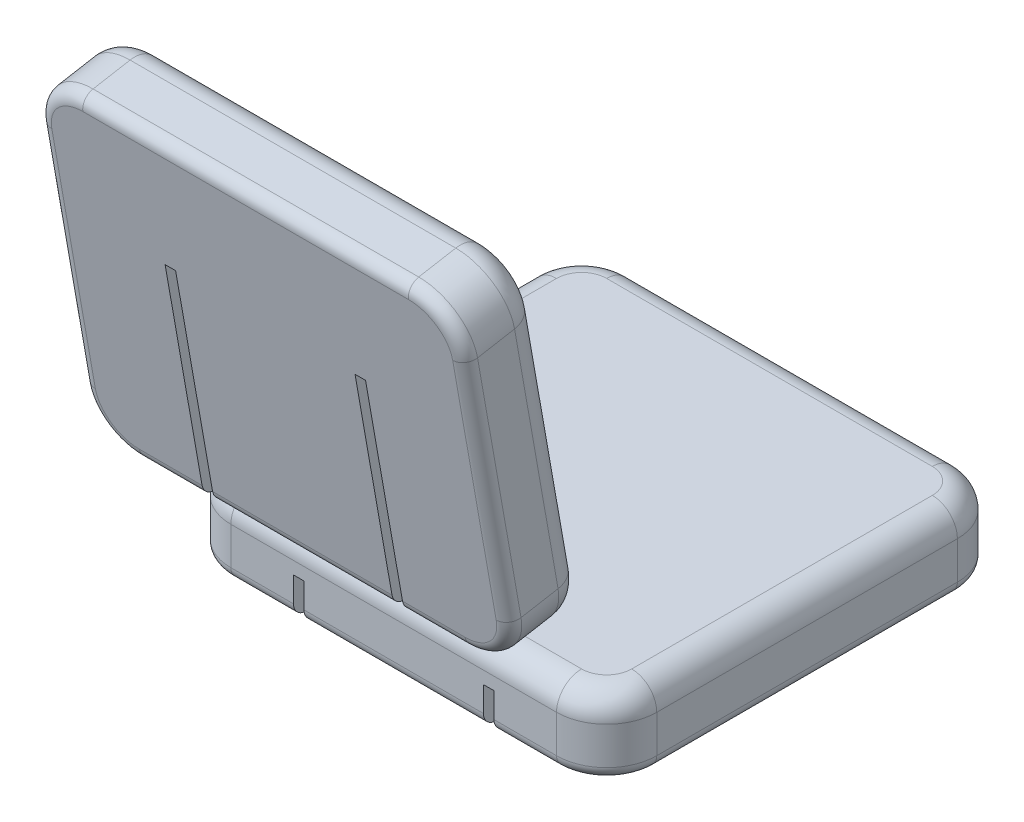
SolidWorks part; units mm, degrees
other "cushion_back"
other "cushion_bottom"
ref_plane "Front" through (0, 0, 0) normal (0, 0, 1) x (1, 0, 0)
ref_plane "Top" through (0, 0, 0) normal (0, 1, 0) x (1, 0, 0)
ref_plane "Right" through (0, 0, 0) normal (1, 0, 0) x (0, 0, -1)
sketch "Sketch1" plane through (0, 0, 0) normal (1, 0, 0) x (0, 0, -1)
  line L0 (-84.1955, -182.4) -> (-80, -182.4) construction
  line L1 (-136.5723, -4.3259) -> (-108.8157, -161.7412) construction
  line L2 (-131.2503, -34.5085) -> (-136.5723, -4.3259) construction
  line L3 (-116.4781, -31.9038) -> (-131.2503, -34.5085) construction
  line L4 (-94.0436, -159.1365) -> (-116.4781, -31.9038) construction
  line L5 (-84.1955, -167.4) -> (-80, -167.4) construction
  line L6 (185.7877, -52.3656) -> (265.7877, -52.3656) construction
  line L7 (265.7877, -52.3656) -> (258.3511, -137.3656) construction
  line L8 (258.3511, -137.3656) -> (193.2242, -137.3656) construction
  line L9 (40, -182.4) -> (40, -252.4) construction
  line L10 (-70, -182.4) -> (-70, -212.4) construction
  line L11 (-86.0777, -117.9317) -> (-110.3884, 19.9414) construction
  line L12 (-110.3884, 19.9414) -> (-139.9327, 14.7319) construction
  line L13 (-139.9327, 14.7319) -> (-115.6219, -123.1412) construction
  line L14 (-86.0777, -117.9317) -> (-115.6219, -123.1412) construction
  line L15 (-80, -152.4) -> (-80, -182.4) construction
  line L16 (80, -152.4) -> (-80, -152.4) construction
  line L17 (80, -152.4) -> (80, -182.4) construction
  line L18 (80, -182.4) -> (-80, -182.4) construction
  line L19 (165.8638, -54.1087) -> (185.7877, -52.3656) construction
  line L20 (165.8638, -54.1087) -> (183.2949, -253.3477) construction
  line L21 (183.2949, -253.3477) -> (203.2188, -251.6045) construction
  line L22 (203.2188, -251.6045) -> (185.7877, -52.3656) construction
  line L23 (-105, -212.4) -> (-135, -242.4) construction
  line L24 (-135, -242.4) -> (-137, -242.4) construction
  line L25 (-137, -242.4) -> (-137, -272.4) construction
  line L26 (-137, -272.4) -> (252, -272.4) construction
  line L27 (252, -272.4) -> (252, -242.4) construction
  line L28 (252, -242.4) -> (250, -242.4) construction
  line L29 (250, -242.4) -> (220, -212.4) construction
  line L30 (220, -212.4) -> (170, -212.4) construction
  line L31 (170, -212.4) -> (130, -252.4) construction
  line L32 (130, -252.4) -> (-15, -252.4) construction
  line L33 (-15, -252.4) -> (-55, -212.4) construction
  line L34 (-55, -212.4) -> (-105, -212.4) construction
  line L35 (-84.1955, -182.4) -> (-80, -182.4)
  line L36 (-136.5723, -4.3259) -> (-108.8157, -161.7412)
  line L37 (-131.2503, -34.5085) -> (-136.5723, -4.3259)
  line L38 (-116.4781, -31.9038) -> (-131.2503, -34.5085)
  line L39 (-94.0436, -159.1365) -> (-116.4781, -31.9038)
  line L40 (-84.1955, -167.4) -> (-80, -167.4)
  line L41 (185.7877, -52.3656) -> (265.7877, -52.3656)
  line L42 (265.7877, -52.3656) -> (258.3511, -137.3656)
  line L43 (258.3511, -137.3656) -> (193.2242, -137.3656)
  line L44 (40, -182.4) -> (40, -252.4)
  line L45 (-70, -182.4) -> (-70, -212.4)
  line L46 (-86.0777, -117.9317) -> (-110.3884, 19.9414)
  line L47 (-110.3884, 19.9414) -> (-139.9327, 14.7319)
  line L48 (-139.9327, 14.7319) -> (-115.6219, -123.1412)
  line L49 (-86.0777, -117.9317) -> (-115.6219, -123.1412)
  line L50 (-80, -152.4) -> (-80, -182.4)
  line L51 (80, -152.4) -> (-80, -152.4)
  line L52 (80, -152.4) -> (80, -182.4)
  line L53 (80, -182.4) -> (-80, -182.4)
  line L54 (165.8638, -54.1087) -> (185.7877, -52.3656)
  line L55 (165.8638, -54.1087) -> (183.2949, -253.3477)
  line L56 (183.2949, -253.3477) -> (203.2188, -251.6045)
  line L57 (203.2188, -251.6045) -> (185.7877, -52.3656)
  line L58 (-105, -212.4) -> (-135, -242.4)
  line L59 (-135, -242.4) -> (-137, -242.4)
  line L60 (-137, -242.4) -> (-137, -272.4)
  line L61 (-137, -272.4) -> (252, -272.4)
  line L62 (252, -272.4) -> (252, -242.4)
  line L63 (252, -242.4) -> (250, -242.4)
  line L64 (250, -242.4) -> (220, -212.4)
  line L65 (220, -212.4) -> (170, -212.4)
  line L66 (170, -212.4) -> (130, -252.4)
  line L67 (130, -252.4) -> (-15, -252.4)
  line L68 (-15, -252.4) -> (-55, -212.4)
  line L69 (-55, -212.4) -> (-105, -212.4)
  arc A0 (-108.8157, -161.7412) -> (-84.1955, -182.4) centre (-84.1955, -157.4) ccw construction
  arc A1 (-94.0436, -159.1365) -> (-84.1955, -167.4) centre (-84.1955, -157.4) ccw construction
  circle A2 centre (195, -272.4) radius 37.5 construction
  circle A3 centre (-80, -272.4) radius 37.5 construction
  arc A4 (-108.8157, -161.7412) -> (-84.1955, -182.4) centre (-84.1955, -157.4) ccw
  arc A5 (-94.0436, -159.1365) -> (-84.1955, -167.4) centre (-84.1955, -157.4) ccw
  circle A6 centre (195, -272.4) radius 37.5
  circle A7 centre (-80, -272.4) radius 37.5
extrude "Boss-Extrude1" add sketch "Sketch1" along normal mid plane 170 contours L53 L52 L51 L50 | L49 L46 L47 L48 L36 L38 L39 | L49 L39 L38 L36 region at (0, -167.4, 0) region at (0, -77.5225, 116.05) region at (0, -39.3208, 111.5629)
fillet "Fillet5" radius 5 4 edges at (0, 14.7319, 139.9327) (85, -54.2046, 127.7773) (0, -123.1412, 115.6219) (-85, -54.2046, 127.7773)
fillet "Fillet6" radius 5 4 edges at (0, -182.4, 80) (85, -182.4, 0) (0, -182.4, -80) (-85, -182.4, 0)
sketch "Sketch2" plane through (0, 0, 0) normal (1, 0, 0) x (0, 0, -1)
  line L0 (-136.5723, -4.3259) -> (-108.8157, -161.7412) construction
  line L1 (-84.1955, -167.4) -> (-80, -167.4) construction
  line L2 (-94.0436, -159.1365) -> (-116.4781, -31.9038) construction
  line L3 (-116.4781, -31.9038) -> (-131.2503, -34.5085) construction
  line L5 (-84.1955, -182.4) -> (-80, -182.4) construction
  line L6 (-131.2503, -34.5085) -> (-108.8157, -161.7412)
  line L7 (-84.1955, -167.4) -> (-80, -167.4)
  line L8 (-94.0436, -159.1365) -> (-116.4781, -31.9038)
  line L9 (-116.4781, -31.9038) -> (-131.2503, -34.5085)
  line L10 (-80, -167.4) -> (20, -167.4)
  line L11 (-84.1955, -182.4) -> (-80, -182.4)
  line L12 (20, -167.4) -> (20, -182.4)
  line L13 (20, -182.4) -> (-80, -182.4)
  line L14 (80, -152.4) -> (80, -182.4) construction
  arc A0 (-94.0436, -159.1365) -> (-84.1955, -167.4) centre (-84.1955, -157.4) ccw construction
  arc A1 (-108.8157, -161.7412) -> (-84.1955, -182.4) centre (-84.1955, -157.4) ccw construction
  arc A2 (-94.0436, -159.1365) -> (-84.1955, -167.4) centre (-84.1955, -157.4) ccw
  arc A3 (-108.8157, -161.7412) -> (-84.1955, -182.4) centre (-84.1955, -157.4) ccw
  dimension "D1" = 60
extrude "Cut-Extrude1" cut sketch "Sketch2" along normal blind 4.2 from offset 40 offset against normal yes
mirror "Mirror1" about plane through (0, 0, 0) normal (1, 0, 0) of "Cut-Extrude1"
fillet "Fillet1" radius 20 8 edges at (85, -164.9, -80) (85, -164.9, 80) (-85, -164.9, 80) (-85, -164.9, -80) (-83.5355, -180.9355, -78.5355) (-83.5355, -180.9355, 78.5355) (83.5355, -180.9355, 78.5355) (83.5355, -180.9355, -78.5355)
fillet "Fillet2" radius 20 8 edges at (85, -120.1023, 98.3878) (85, 17.7708, 122.6985) (-85, -120.1023, 98.3878) (-85, 17.7708, 122.6985) (-83.5355, 13.544, 138.2361) (-83.5355, -121.4447, 114.434) (83.5355, 13.544, 138.2361) (83.5355, -121.4447, 114.434)
fillet "Fillet3" radius 10 8 edges at (79.1421, 14.1725, 109.3712) (0, 19.9414, 110.3884) (-79.1421, 14.1725, 109.3712) (-85, -48.9952, 98.2331) (-79.1421, -112.1629, 87.0949) (0, -117.9317, 86.0777) (79.1421, -112.1629, 87.0949) (85, -48.9952, 98.2331)
fillet "Fillet4" radius 10 8 edges at (79.1421, -152.4, 74.1421) (0, -152.4, 80) (-79.1421, -152.4, 74.1421) (-85, -152.4, 0) (-79.1421, -152.4, -74.1421) (0, -152.4, -80) (79.1421, -152.4, -74.1421) (85, -152.4, 0)
sketch "Sketch3" plane through (0, -182.4, 0) normal (0, -1, 0) x (1, 0, 0)
  line L0 (-25.2, 30) -> (-25.2, 0)
  line L1 (-20, -5.2) -> (20, -5.2)
  line L2 (25.2, 0) -> (25.2, 30)
  line L3 (20, 35.2) -> (-20, 35.2)
  line L4 (20, 35) -> (-20, 35)
  line L5 (-25, 30) -> (-25, 0)
  line L6 (-20, -5) -> (20, -5)
  line L7 (25, 0) -> (25, 30)
  line L8 (20, 35) -> (-20, 35) construction
  line L9 (-25, 30) -> (-25, 0) construction
  line L10 (-20, -5) -> (20, -5) construction
  line L11 (25, 0) -> (25, 30) construction
  arc A0 (-25.2, 0) -> (-20, -5.2) centre (-20, 0) ccw
  arc A1 (20, -5.2) -> (25.2, 0) centre (20, 0) ccw
  arc A2 (25.2, 30) -> (20, 35.2) centre (20, 30) ccw
  arc A3 (-20, 35.2) -> (-25.2, 30) centre (-20, 30) ccw
  arc A4 (-20, 35) -> (-25, 30) centre (-20, 30) ccw
  arc A5 (-25, 0) -> (-20, -5) centre (-20, 0) ccw
  arc A6 (20, -5) -> (25, 0) centre (20, 0) ccw
  arc A7 (25, 30) -> (20, 35) centre (20, 30) ccw
  arc A8 (-20, 35) -> (-25, 30) centre (-20, 30) ccw construction
  arc A9 (-25, 0) -> (-20, -5) centre (-20, 0) ccw construction
  arc A10 (20, -5) -> (25, 0) centre (20, 0) ccw construction
  arc A11 (25, 30) -> (20, 35) centre (20, 30) ccw construction
  dimension "D1" = 0
  dimension "D2" = 0.2
extrude "Cut-Extrude3" cut sketch "Sketch3" against normal offset from surface (13 mm away) 2
fillet "Fillet7" radius 2 16 edges at (23.677, -182.4, 33.677) (25.2, -182.4, 15) (23.677, -182.4, -3.677) (0, -182.4, -5.2) (-23.677, -182.4, -3.677) (-25.2, -182.4, 15) (-23.677, -182.4, 33.677) (-23.677, -169.4, 33.677) (-25.2, -169.4, 15) (-23.677, -169.4, -3.677) (0, -169.4, -5.2) (23.677, -169.4, -3.677) (25.2, -169.4, 15) (23.677, -169.4, 33.677) (0, -182.4, 35.2) (0, -169.4, 35.2)
